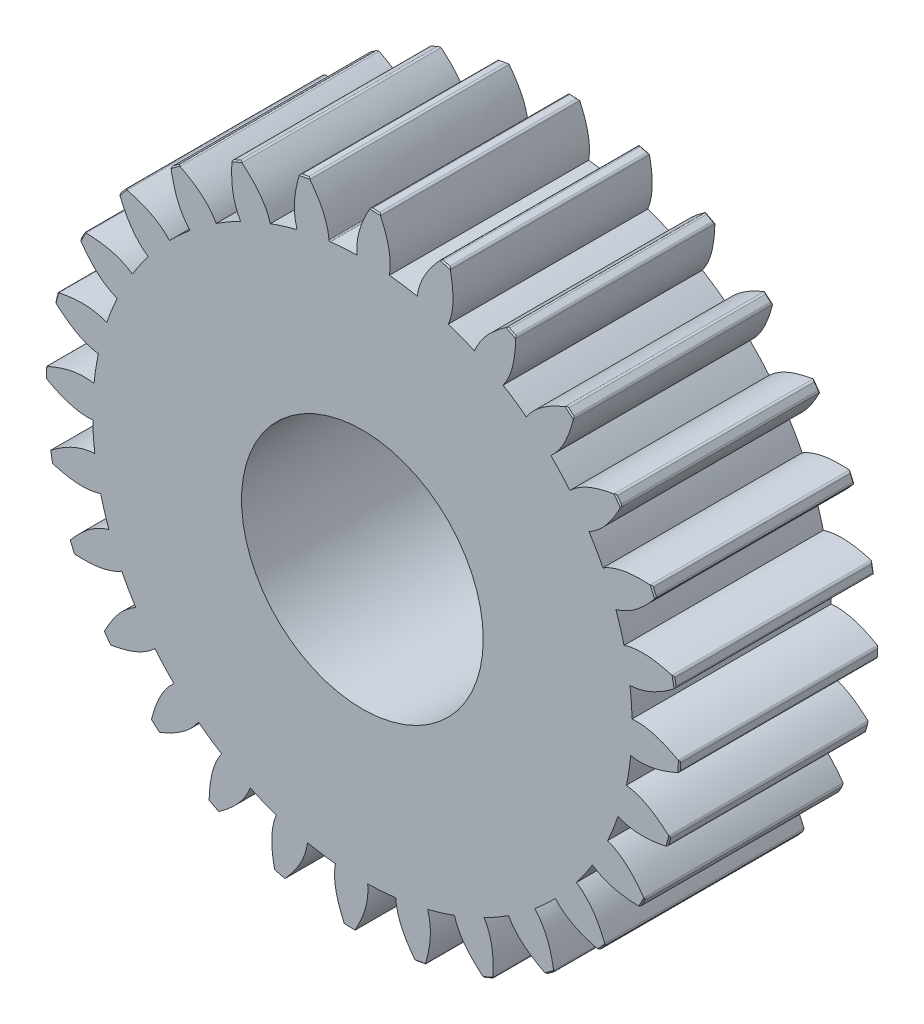
SolidWorks part; units mm, degrees
ref_plane "Front Plane" through (0, 0, 0) normal (0, 0, 1) x (1, 0, 0)
ref_plane "Top Plane" through (0, 0, 0) normal (0, 1, 0) x (1, 0, 0)
ref_plane "Right Plane" through (0, 0, 0) normal (1, 0, 0) x (0, 0, -1)
sketch "Sketch1" plane through (0, 0, 0) normal (0, 0, 1) x (1, 0, 0)
  line L0 (-11.1702, 45.0096) -> (-8.444, 45.3508) construction
  line L1 (-0.2653, 46.3742) -> (10.6546, 45.1345) construction
  line L2 (10.6546, 45.1345) -> (20.976, 41.36) construction
  line L3 (20.976, 41.36) -> (30.1195, 35.2627) construction
  line L4 (-0.2653, 46.3742) -> (-11.2553, 46.3742) construction
  line L5 (10.6546, 45.1345) -> (-10.7375, 50.1843) construction
  line L6 (20.976, 41.36) -> (-8.4285, 56.2727) construction
  line L7 (30.1195, 35.2627) -> (-3.3068, 63.8137) construction
  line L8 (0, 0) -> (-5.541, 44.2797) construction
  line L10 (0, 0) -> (-8.444, 45.3508) construction
  circle A0 centre (0, 0) radius 49 construction
  circle A1 centre (0, 0) radius 46.375
  circle A2 centre (0, 0) radius 44.625
  arc A4 (-8.8299, 51.7521) -> (-10.3878, 51.4621) centre (0, 0) ccw
  spline S0 degree 3 poles (-10.7876, 43.3015) (-10.9725, 43.8672) (-11.1951, 44.89) (-11.3302, 47.1995) (-10.9721, 49.3735) (-10.5153, 51.0397) (-10.3878, 51.4621) knots -0.082666 -0.082666 -0.082666 -0.082666 0 0.065609 0.250118 0.313483 0.313483 0.313483 0.313483
  spline S1 degree 3 poles (-5.5199, 44.2823) (-5.5757, 45.3484) (-6.1221, 47.6135) (-7.5332, 50.0138) (-8.559, 51.4039) (-8.8299, 51.7521) knots -0.082666 -0.082666 -0.082666 -0.082666 0.065609 0.250118 0.313483 0.313483 0.313483 0.313483
  dimension "D2" = 98
  dimension "D3" = 92.75
  dimension "D4" = 89.25
  dimension "D5" = 10.99
  dimension "D6" = 10.99
  dimension "D7" = 21.98
  dimension "D8" = 32.97
  dimension "D9" = 43.96
extrude "Boss-Extrude2" add sketch "Sketch1" along normal blind 32.97 contours A1 S1 A4 S0 | A2 S1 A1 S0 | A2
fillet "Fillet1" radius 0.2 2 edges at (-10.7876, 43.3015, 16.485) (-5.5199, 44.2823, 16.485)
chamfer "Chamfer1" distance 0.2 angle 45 2 edges at (-9.61, 51.613, 0) (-9.61, 51.613, 32.97)
fillet "Fillet2" radius 0.4 2 edges at (-8.8299, 51.7521, 16.485) (-10.3878, 51.4621, 16.485)
pattern_circular "CirPattern2" count 28 over 360 about axis through (0, 0, 32.97) along (0, 0, 1) of "Boss-Extrude2", "Chamfer1", "Fillet2"
sketch "Sketch2" plane through (0, 0, 32.97) normal (0, 0, 1) x (1, 0, 0)
  circle A0 centre (0, 0) radius 20
  dimension "D1" = 40
extrude "Cut-Extrude1" cut sketch "Sketch2" against normal through all
